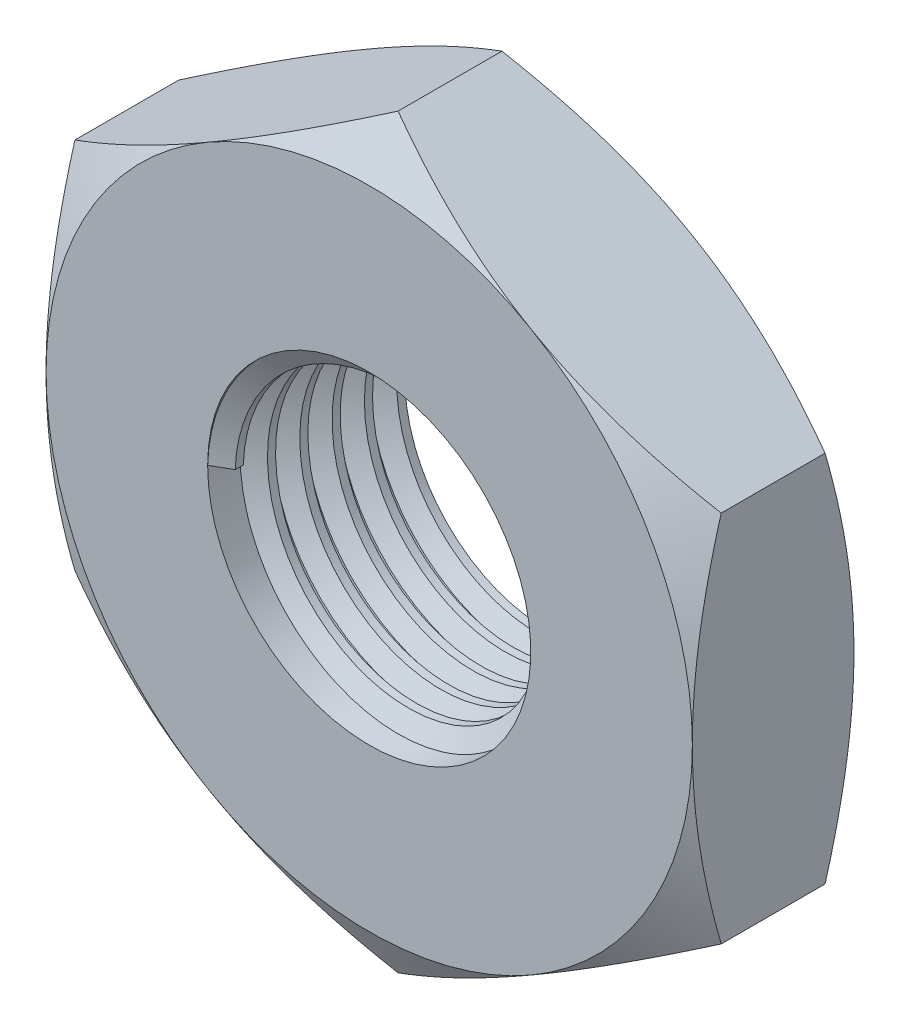
SolidWorks part; units mm, degrees
ref_plane "Front Plane" through (0, 0, 0) normal (0, 0, 1) x (1, 0, 0)
ref_plane "Top Plane" through (0, 0, 0) normal (0, 1, 0) x (1, 0, 0)
ref_plane "Right Plane" through (0, 0, 0) normal (1, 0, 0) x (0, 0, -1)
sketch "Sketch1" plane through (0, 0, 0) normal (0, 0, 1) x (1, 0, 0)
  line L1 (0, 11.547) -> (-10, 5.7735)
  line L2 (-10, 5.7735) -> (-10, -5.7735)
  line L3 (-10, -5.7735) -> (0, -11.547)
  line L4 (0, -11.547) -> (10, -5.7735)
  line L5 (10, -5.7735) -> (10, 5.7735)
  line L6 (10, 5.7735) -> (0, 11.547)
  circle A0 centre (0, 0) radius 10 construction
  circle A1 centre (0, 0) radius 5
  dimension "D1" = 20
extrude "Boss-Extrude1" add sketch "Sketch1" along normal mid plane 5
sketch "Sketch2" plane through (0, 0, 2.5) normal (0, 0, 1) x (1, 0, 0)
  circle A0 centre (0, 0) radius 10
extrude "Cut-Extrude1" cut sketch "Sketch2" against normal through all draft 60 flip side to cut
mirror "Mirror1" about plane through (0, 0, 0) normal (0, 0, 1) of "Cut-Extrude1"
thread "Thread1" pitch 1 method extrude profile "Thread Profile1" start angle 0, offset 0, length 5, pitch 1, diameter 10
ref_plane "Plane1" through (-5, 0, 2.5) normal (0, -1, 0) x (-1, 0, 0)
sketch "Thread Profile1" plane through (-5, 0, 2.5) normal (0, -1, 0) x (-1, 0, 0)
  line L0 (0, 0) -> (0, 1) construction
  line L11 (0, 0) -> (0, 0.875)
  line L12 (0, 0.875) -> (-0.5413, 0.5625)
  line L13 (-0.5413, 0.5625) -> (-0.5413, 0.3125)
  line L15 (-0.5413, 0.3125) -> (0, 0)
  line L17 (-0.5413, 0.4375) -> (0, 0.4375) construction
  point P2 (0, 0)
  dimension "Pitch" = 1
  dimension "Profile_Angle" = 60
  dimension "Profile_Land" = 0.25
  dimension "Profile_Height" = 0.5413
